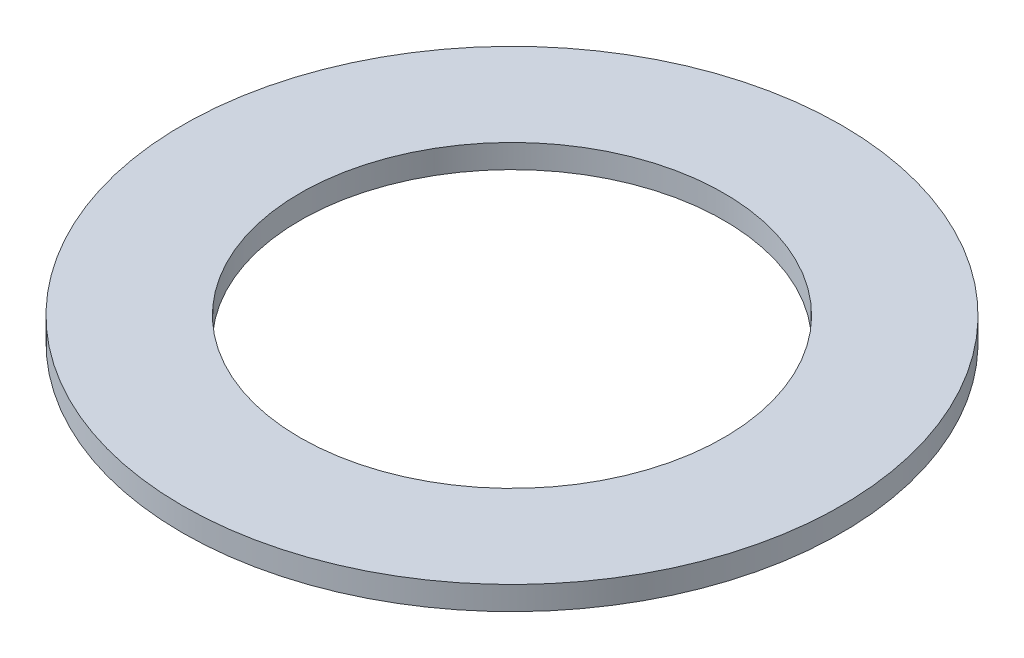
SolidWorks part; units mm, degrees
ref_plane "Front Plane" through (0, 0, 0) normal (0, 0, 1) x (1, 0, 0)
ref_plane "Top Plane" through (0, 0, 0) normal (0, 1, 0) x (1, 0, 0)
ref_plane "Right Plane" through (0, 0, 0) normal (1, 0, 0) x (0, 0, -1)
sketch "Sketch1" plane through (0, 0, 0) normal (0, 1, 0) x (1, 0, 0)
  circle A0 centre (0, 0) radius 70
  dimension "FLANGE_OD" = 140
extrude "Boss-Extrude1" add sketch "Sketch1" along normal blind 5
sketch "Sketch2" plane through (0, 0, 0) normal (0, 1, 0) x (1, 0, 0)
  circle A0 centre (0, 0) radius 45
  dimension "BORE_D" = 90
extrude "Cut-Extrude1" cut sketch "Sketch2" along normal through all
sketch "Sketch3" plane through (0, 5, 0) normal (0, 1, 0) x (1, 0, 0)
  circle A0 centre (0, 0) radius 27.6952 construction
  circle A1 centre (-27.6952, 0) radius 2.3142
  dimension "BOLT_D" = 4.6285
  dimension "BOLT_PCD" = 55.3904
extrude "Cut-Extrude2" cut sketch "Sketch3" against normal blind 3.5301 rebuild error yes
pattern_circular "CirPattern1" count 4 over 360 rebuild error yes
